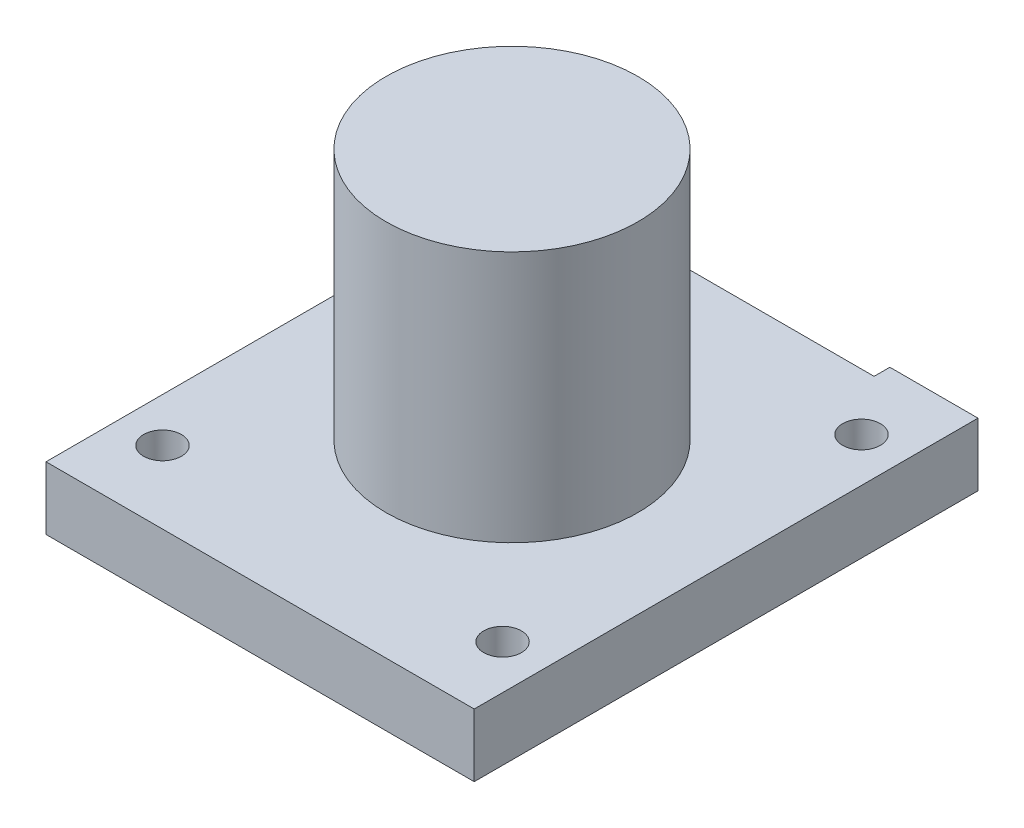
SolidWorks part; units mm, degrees
ref_plane "前视基准面" through (0, 0, 0) normal (0, 0, 1) x (1, 0, 0)
ref_plane "上视基准面" through (0, 0, 0) normal (0, 1, 0) x (1, 0, 0)
ref_plane "右视基准面" through (0, 0, 0) normal (1, 0, 0) x (0, 0, -1)
sketch "草图1" plane through (0, 0, 0) normal (0, 1, 0) x (1, 0, 0)
  line L1 (0, 0) -> (24, 0)
  line L2 (0, 0) -> (0, 24)
  line L3 (0, 24) -> (24, 24)
  line L4 (24, 0) -> (24, 24)
  circle A0 centre (12, 12) radius 10
extrude "凸台-拉伸1" add sketch "草图1" along normal blind 20 contours A0 region at (12, 0, -12)
sketch "草图4" plane through (0, 0, 0) normal (0, 1, 0) x (1, 0, 0)
  line L0 (29, 32) -> (22, 32)
  line L1 (-5, -8) -> (29, -8)
  line L2 (-5, -8) -> (-5, 32)
  line L3 (2, 32) -> (-5, 32)
  line L4 (29, -8) -> (29, 32)
  line L6 (-5, 12) -> (29, 12) construction
  line L7 (12, 30.75) -> (22, 30.75)
  line L8 (22, 30.75) -> (22, 32)
  line L9 (12, 30.75) -> (2, 30.75)
  line L10 (2, 30.75) -> (2, 32)
  circle A0 centre (12, 12) radius 10
extrude "凸台-拉伸3" add sketch "草图4" against normal blind 5 contours L1 L4 L2 A0 | L2 L6 A0 L4 L0 L8 L7 L9 L10 L3 region at (12, 0, -23.3451) region at (12, 0, -0.271)
sketch "草图5" plane through (0, 0, 0) normal (0, 1, 0) x (1, 0, 0)
  line L0 (-3, 12) -> (27, 12) construction
  line L1 (12, 30.75) -> (12, -6.75) construction
  circle A0 centre (-1.5, 26.25) radius 1.5
  circle A1 centre (-1.5, -2.25) radius 1.5
  circle A2 centre (25.5, -2.25) radius 1.5
  circle A3 centre (25.5, 26.25) radius 1.5
extrude "凸台-拉伸4" add sketch "草图4<4>" against normal blind 3 contours A0 | A0 L6 region at (12, 0, -7.7559) region at (12, 0, -16.2441)
sketch "草图4<4>" plane through (0, 0, 0) normal (0, 1, 0) x (1, 0, 0) same geometry as "草图4"
extrude "切除-拉伸1" cut sketch "草图5" against normal blind 10
